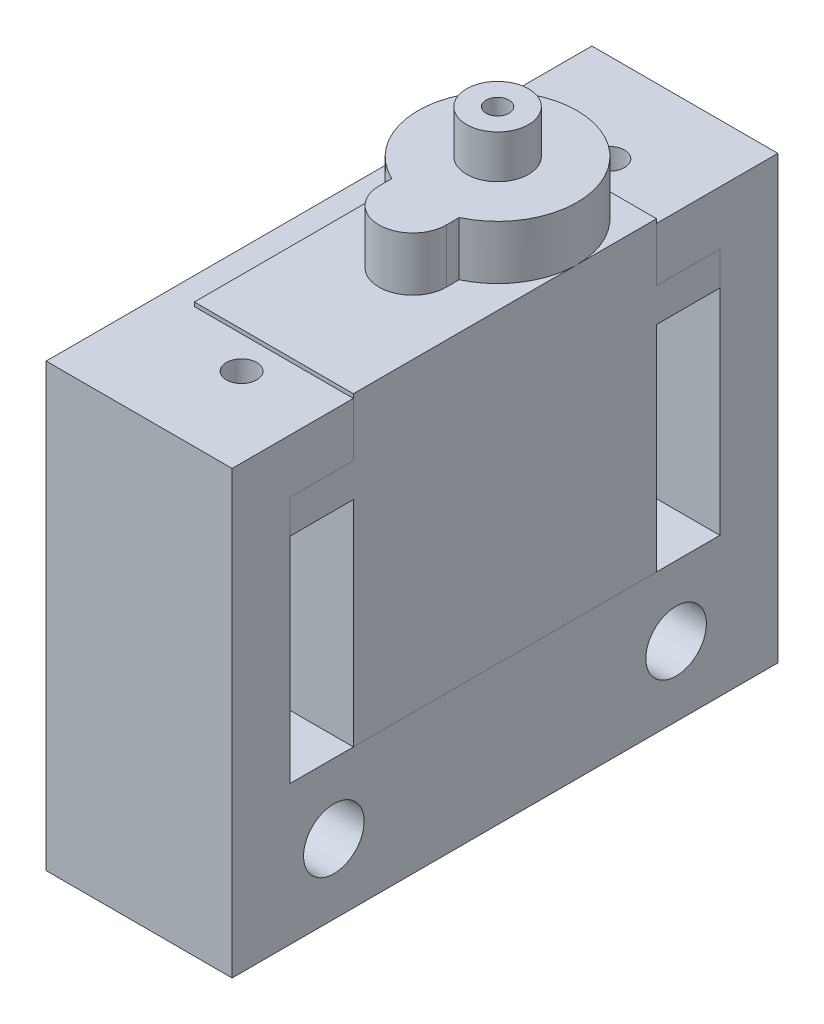
SolidWorks part; units mm, degrees
ref_plane "Plan de face" through (0, 0, 0) normal (0, 0, 1) x (1, 0, 0)
ref_plane "Plan de dessus" through (0, 0, 0) normal (0, 1, 0) x (1, 0, 0)
ref_plane "Plan de droite" through (0, 0, 0) normal (1, 0, 0) x (0, 0, -1)
sketch "Esquisse1" plane through (0, 0, 0) normal (1, 0, 0) x (0, 0, -1)
  line L0 (11.25, 0) -> (-11.25, 0) construction
  line L1 (0, 14.95) -> (0, -14.95) construction
  line L2 (-11.25, -14.95) -> (11.25, -14.95)
  line L3 (11.25, -14.95) -> (11.25, 0.95)
  line L4 (11.25, 0.95) -> (15.95, 0.95)
  line L5 (15.95, 0.95) -> (15.95, 3.45)
  line L6 (15.95, 3.45) -> (11.25, 3.45)
  line L7 (11.25, 3.45) -> (11.25, 7.75)
  line L8 (11.25, 7.75) -> (-11.25, 7.75)
  line L9 (-11.25, 7.75) -> (-11.25, 3.45)
  line L10 (-11.25, 3.45) -> (-15.95, 3.45)
  line L11 (-15.95, 3.45) -> (-15.95, 0.95)
  line L12 (-15.95, 0.95) -> (-11.25, 0.95)
  line L13 (-11.25, 0.95) -> (-11.25, -14.95)
  point P4 (0, 0)
  point P8 (0, 0)
  dimension "D1" = 15.9
  dimension "D2" = 2.5
  dimension "D3" = 4.7
  dimension "D4" = 22.5
  dimension "D5" = 4.7
  dimension "D6" = 4.3
  dimension "D7" = 2.5
  dimension "D8" = 15.9
  dimension "D9" = 22.5
  dimension "D10" = 18.4
  dimension "D11" = 22.7
extrude "Boss.-Extru.1" add sketch "Esquisse1" along normal blind 5.9 and the other way blind 5.9
sketch "Esquisse2" plane through (0, 7.75, 0) normal (0, 1, 0) x (1, 0, 0)
  line L0 (-5.9, 11.25) -> (5.9, 11.25) construction
  line L1 (-5.9, 11.25) -> (5.9, 11.25) construction
  line L2 (-2.5, 0.0058) -> (2.5, 0.0058) construction
  line L3 (0, 5.35) -> (0, -3.45) construction
  line L4 (-2.5, 0.0058) -> (-2.5, -3.45) construction
  line L5 (-2.5, -3.45) -> (2.5, -3.45) construction
  line L6 (2.5, -3.45) -> (2.5, 0.0058) construction
  line L7 (-2.5, -0.95) -> (-2.5, 0.0058)
  line L8 (2.5, -0.95) -> (2.5, 0.0058)
  arc A0 (2.5, 0.0058) -> (-2.5, 0.0058) centre (0, 5.35) ccw
  arc A1 (-2.5, -0.95) -> (2.5, -0.95) centre (0, -0.95) ccw
  point P6 (-2.5, -1.7221)
  point P11 (2.5, -1.7221)
extrude "Boss.-Extru.2" add sketch "Esquisse2" along normal blind 4
sketch "Esquisse3" plane through (0, 3.45, 0) normal (0, 1, 0) x (1, 0, 0)
  line L0 (0, 18.25) -> (0, 11.25) construction
  line L1 (0, 11.25) -> (7.0868, 11.25) construction
  line L2 (0, 15.95) -> (0, 13.65) construction
  line L3 (-5.9, 15.95) -> (5.9, 15.95) construction
  line L4 (-0.65, 15.95) -> (0.65, 15.95) construction
  line L5 (-0.65, 15.95) -> (-0.65, 14.4099)
  line L6 (0.65, 15.95) -> (0.65, 14.4099)
  line L7 (-0.65, 15.95) -> (0.65, 15.95)
  line L8 (0, 0) -> (11.6221, 0) construction
  line L9 (-0.65, -15.95) -> (0.65, -15.95) construction
  line L10 (0, -15.95) -> (0, -13.65) construction
  line L11 (0, -11.25) -> (7.0868, -11.25) construction
  line L12 (0, -18.25) -> (0, -11.25) construction
  line L13 (-0.65, -15.95) -> (0.65, -15.95)
  line L14 (0.65, -15.95) -> (0.65, -14.4099)
  line L15 (-0.65, -15.95) -> (-0.65, -14.4099)
  arc A0 (2.5, 0.0058) -> (-2.5, 0.0058) centre (0, 5.35) ccw construction
  arc A1 (-0.65, 14.4099) -> (0.65, 14.4099) centre (0, 13.65) ccw
  arc A2 (-0.65, -14.4099) -> (0.65, -14.4099) centre (0, -13.65) cw
  point P13 (0, 15.95)
  point P27 (0, -15.95)
extrude "Enlèv. mat.-Extru.1" cut sketch "Esquisse3" against normal up to surface (2.5 mm away) up to face at (0, 0.95, -13.6)
sketch "Esquisse4" plane through (0, 11.75, 0) normal (0, 1, 0) x (1, 0, 0)
  circle A0 centre (0, 5.35) radius 2.3
  circle A1 centre (0, 5.35) radius 0.85
extrude "Boss.-Extru.3" add sketch "Esquisse4" along normal blind 3.2
sketch "Sketch1" plane through (0, 3.45, 0) normal (0, 1, 0) x (1, 0, 0)
  line L0 (5.9, -11.25) -> (-5.9, -11.25)
  line L1 (5.9, -11.25) -> (5.9, -20.25)
  line L2 (-5.9, -11.25) -> (-5.9, -20.25)
  line L3 (5.9, -20.25) -> (-5.9, -20.25)
  circle A0 centre (0, -13.65) radius 1.125
  dimension "D2" = 2.25
  dimension "D1" = 9
extrude "Boss-Extrude1" add sketch "Sketch1" along normal blind 4 separate body
sketch "Sketch3" plane through (0, 3.45, 0) normal (0, -1, 0) x (1, 0, 0)
  line L1 (-5.9, 15.95) -> (5.9, 15.95)
  line L2 (-5.9, 15.95) -> (-5.9, 20.25)
  line L3 (-5.9, 20.25) -> (5.9, 20.25)
  line L4 (5.9, 15.95) -> (5.9, 20.25)
extrude "Boss-Extrude2" add sketch "Sketch3" along normal offset from surface (22.4 mm away) 4 separate body up to face at (0, -14.95, 0) offset beyond the face yes
sketch "Sketch4" plane through (0, -14.95, 0) normal (0, -1, 0) x (1, 0, 0)
  line L0 (-5.9, 0) -> (5.9, 0)
  line L1 (-5.9, 11.25) -> (5.9, 11.25)
  line L2 (-5.9, 11.25) -> (-5.9, -11.25)
  line L3 (-5.9, -11.25) -> (5.9, -11.25)
  line L4 (5.9, 11.25) -> (5.9, -11.25)
sketch "Sketch5" plane through (0, 0, 15.95) normal (0, 0, -1) x (-1, 0, 0)
  line L0 (5.9, -18.95) -> (5.9, 3.45) construction
  line L1 (-5.9, -18.95) -> (5.9, -18.95)
  line L2 (-5.9, -18.95) -> (-5.9, -14.95)
  line L3 (-5.9, -14.95) -> (5.9, -14.95)
  line L4 (5.9, -18.95) -> (5.9, -14.95)
  dimension "D1" = 4
extrude "Boss-Extrude3" add sketch "Sketch5" along normal up to vertex (15.95 mm away) separate body up to point (-5.9, -14.95, 0)
combine bodies "Combine1" operation type add bodies to combine 107 106 105
ref_plane "Plane1" through (0, 0, 0) normal (0, 0, -1) x (-1, 0, 0)
mirror "Mirror3" about plane through (0, 0, 0) normal (0, 0, -1) of "Boss-Extrude1", "Boss-Extrude2", "Boss-Extrude3"
sketch "Sketch6" plane through (0, -18.95, 0) normal (0, -1, 0) x (1, 0, 0)
  line L1 (-5.9, 20.25) -> (5.9, 20.25)
  line L2 (-5.9, 20.25) -> (-5.9, -20.25)
  line L3 (-5.9, -20.25) -> (5.9, -20.25)
  line L4 (5.9, 20.25) -> (5.9, -20.25)
extrude "Boss-Extrude4" add sketch "Sketch6" along normal blind 6.35
sketch "Sketch7" plane through (-5.9, 0, 0) normal (-1, 0, 0) x (0, 0, 1)
  line L0 (0, -25.3) -> (0, -14.95)
  line L1 (20.25, -25.3) -> (-20.25, -25.3) construction
  line L2 (11.25, -14.95) -> (-11.25, -14.95) construction
  line L3 (12.7, -20.125) -> (-12.7, -20.125)
  circle A0 centre (12.7, -20.125) radius 2.2479
  circle A1 centre (-12.7, -20.125) radius 2.2479
  point P9 (0, -20.125)
  dimension "D1" = 4.4958
  dimension "D2" = 25.4
extrude "Cut-Extrude1" cut sketch "Sketch7" against normal through all contours A0 | A1 region at (-5.9, -20.125, -14.8843) region at (-5.9, -17.9407, 12.7)
sketch "Sketch8" plane through (-5.9, 0, 0) normal (-1, 0, 0) x (0, 0, 1)
  line L1 (20.25, -25.3) -> (-20.25, -25.3)
  line L2 (20.25, -25.3) -> (20.25, 7.45)
  line L3 (20.25, 7.45) -> (-20.25, 7.45)
  line L4 (-20.25, -25.3) -> (-20.25, 7.45)
  circle A1 centre (-12.7, -20.125) radius 2.2479
  circle A3 centre (12.7, -20.125) radius 2.2479
  dimension "D1" = 4.4958
  dimension "D2" = 4.4958
extrude "Boss-Extrude5" add sketch "Sketch8" along normal blind 2
